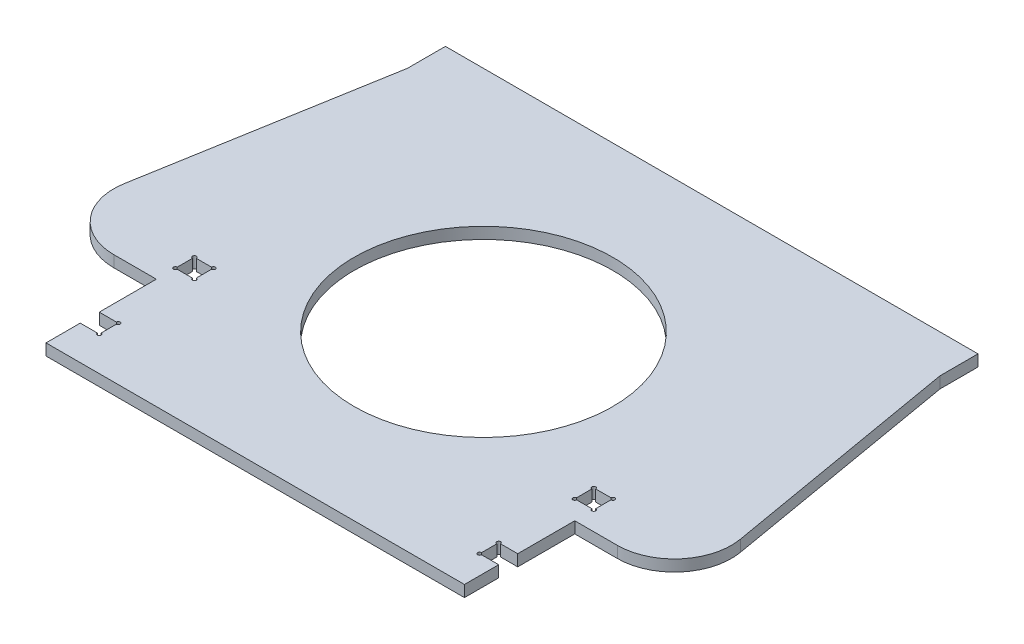
SolidWorks part; units mm, degrees
ref_plane "Front Plane" through (0, 0, 0) normal (0, 0, 1) x (1, 0, 0)
ref_plane "Top Plane" through (0, 0, 0) normal (0, 1, 0) x (1, 0, 0)
ref_plane "Right Plane" through (0, 0, 0) normal (1, 0, 0) x (0, 0, -1)
sketch "Sketch1" plane through (0, 0, 0) normal (0, 1, 0) x (1, 0, 0)
  line L0 (70, 110) -> (70, 120)
  line L1 (55, 29) -> (55, 14)
  line L2 (55, 29) -> (84, 29)
  line L3 (70, 110) -> (84, 29)
  line L4 (70, 120) -> (-70, 120)
  line L5 (0, 120) -> (0, 0) construction
  line L6 (55, 0) -> (-55, 0)
  line L7 (-55, 9) -> (-55, 0)
  line L8 (-55, 29) -> (-84, 29)
  line L9 (-70, 110) -> (-70, 120)
  line L10 (-70, 110) -> (-84, 29)
  line L11 (55, 14) -> (50, 14)
  line L12 (50, 14) -> (50, 9)
  line L13 (50, 9) -> (55, 9)
  line L14 (55, 9) -> (55, 0)
  line L15 (-50, 9) -> (-55, 9)
  line L16 (55, 34) -> (50, 34)
  line L17 (55, 34) -> (55, 39)
  line L18 (55, 39) -> (50, 39)
  line L19 (50, 34) -> (50, 39)
  line L20 (-50, 14) -> (-50, 9)
  line L21 (-55, 14) -> (-50, 14)
  line L22 (-55, 29) -> (-55, 14)
  line L23 (-55, 34) -> (-50, 34)
  line L24 (-55, 34) -> (-55, 39)
  line L25 (-55, 39) -> (-50, 39)
  line L26 (-50, 34) -> (-50, 39)
  dimension "D1" = 5
  dimension "D2" = 70
  dimension "D3" = 10
  dimension "D4" = 55
  dimension "D5" = 29
  dimension "D6" = 120
  dimension "D7" = 29
  dimension "D8" = 5
  dimension "D9" = 5
  dimension "D10" = 9
  dimension "D11" = 170.194
extrude "Boss-Extrude1" add sketch "Sketch1" along normal blind 3
sketch "Sketch2" plane through (0, 3, 0) normal (0, 1, 0) x (1, 0, 0)
  line L0 (0, 120) -> (0, 0) construction
  line L1 (70, 120) -> (-70, 120) construction
  circle A0 centre (0, 60) radius 34
  dimension "D1" = 68
extrude "Cut-Extrude1" cut sketch "Sketch2" against normal blind 3
fillet "Fillet1" radius 15 2 edges at (84, 1.5, -29) (-84, 1.5, -29)
sketch "Sketch4" plane through (0, 3, 0) normal (0, 1, 0) x (1, 0, 0)
  line L0 (55, 39) -> (50, 39) construction
  line L1 (55, 34) -> (55, 39) construction
  line L2 (50, 39) -> (50, 34) construction
  line L3 (50, 34) -> (55, 34) construction
  line L4 (50, 14) -> (55, 14) construction
  line L5 (50, 9) -> (50, 14) construction
  line L6 (0, 0) -> (0, 22.5564) construction
  line L7 (55, 9) -> (50, 9) construction
  arc A0 (54.5, 39) -> (55, 38.5) centre (55, 39) cw
  arc A1 (50.5, 39) -> (50, 38.5) centre (50, 39) ccw
  arc A2 (50, 34.5) -> (50.5, 34) centre (50, 34) ccw
  arc A3 (55, 34.5) -> (54.5, 34) centre (55, 34) cw
  arc A4 (50.5, 14) -> (50, 13.5) centre (50, 14) ccw
  arc A5 (50, 9.5) -> (50.5, 9) centre (50, 9) ccw
  arc A6 (-50, 9.5) -> (-50.5, 9) centre (-50, 9) cw
  arc A7 (-50.5, 14) -> (-50, 13.5) centre (-50, 14) cw
  arc A8 (-50, 34.5) -> (-50.5, 34) centre (-50, 34) cw
  arc A9 (-55, 34.5) -> (-54.5, 34) centre (-55, 34) ccw
  arc A10 (-54.5, 39) -> (-55, 38.5) centre (-55, 39) ccw
  arc A11 (-50.5, 39) -> (-50, 38.5) centre (-50, 39) cw
  line M2 (55, 39) -> (55, 34)
  line M3 (55, 34) -> (50, 34)
  line M4 (50, 34) -> (50, 39)
  line M5 (50, 39) -> (55, 39)
  line M16 (-55, 14) -> (-50, 14)
  line M17 (-50, 14) -> (-50, 9)
  line M18 (-50, 9) -> (-55, 9)
  line M22 (55, 9) -> (50, 9)
  line M23 (50, 9) -> (50, 14)
  line M24 (50, 14) -> (55, 14)
  line M26 (-55, 34) -> (-55, 39)
  line M27 (-55, 39) -> (-50, 39)
  line M28 (-50, 39) -> (-50, 34)
  line M29 (-50, 34) -> (-55, 34)
  dimension "D1" = 0.5
extrude "Cut-Extrude2" cut sketch "Sketch4" against normal through all contours A1 M5 M4 | A0 M5 M2 | A3 M2 M3 | A2 M4 M3 | A4 M24 M23 | A5 M23 M22 | A10 M27 M26 | A11 M27 M28 | A8 M28 M29 | A9 M26 M29 | A7 M16 M17 | A6 M17 M18 region at (55.0707, 3, -39.0707) region at (49.9293, 3, -39.0707) region at (55.0707, 3, -33.9293) region at (49.9293, 3, -33.9293) region at (49.9293, 3, -14.0707) region at (49.9293, 3, -8.9293) region at (-49.9293, 3, -14.0707) region at (-49.9293, 3, -8.9293) region at (-49.9293, 3, -33.9293) region at (-49.9293, 3, -39.0707) region at (-55.0707, 3, -33.9293) region at (-55.0707, 3, -39.0707)
